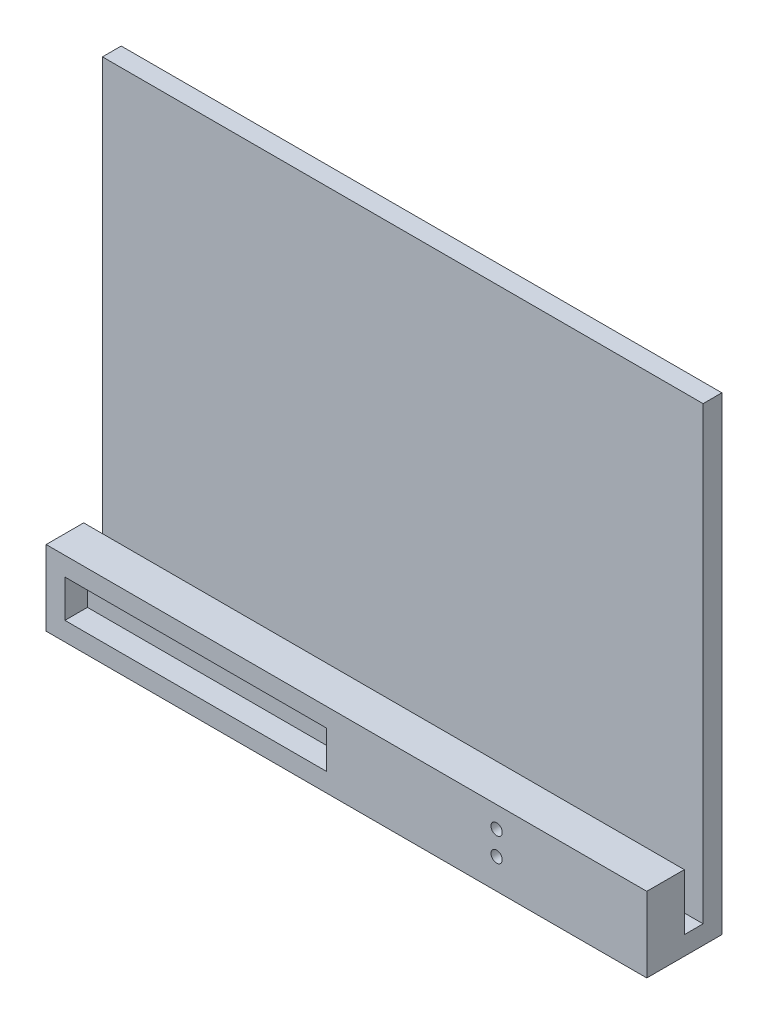
SolidWorks part; units mm, degrees
ref_plane "Front Plane" through (0, 0, 0) normal (0, 0, 1) x (1, 0, 0)
ref_plane "Top Plane" through (0, 0, 0) normal (0, 1, 0) x (1, 0, 0)
ref_plane "Right Plane" through (0, 0, 0) normal (1, 0, 0) x (0, 0, -1)
sketch "Sketch1" plane through (0, 0, 0) normal (0, 0, 1) x (1, 0, 0)
  line L1 (0, 158.75) -> (203.2, 158.75)
  line L2 (0, 158.75) -> (0, 0)
  line L3 (0, 0) -> (203.2, 0)
  line L4 (203.2, 158.75) -> (203.2, 0)
  point P4 (0, 0)
  dimension "D1" = 158.75
  dimension "D2" = 203.2
extrude "Boss-Extrude1" add sketch "Sketch1" along normal blind 6.35
sketch "Sketch2" plane through (0, 0, 6.35) normal (0, 0, 1) x (1, 0, 0)
  line L0 (0, 158.75) -> (0, 0) construction
  line L1 (0, 6.35) -> (203.2, 6.35)
  line L2 (0, 6.35) -> (0, 0)
  line L3 (0, 0) -> (203.2, 0)
  line L4 (203.2, 6.35) -> (203.2, 0)
  dimension "D1" = 6.35
extrude "Boss-Extrude2" add sketch "Sketch2" along normal blind 19.05
sketch "Sketch3" plane through (0, 6.35, 0) normal (0, 1, 0) x (1, 0, 0)
  line L6 (203.2, -25.4) -> (203.2, -6.35) construction
  line L7 (0, -25.4) -> (203.2, -25.4)
  line L8 (0, -25.4) -> (0, -12.7)
  line L9 (0, -12.7) -> (203.2, -12.7)
  line L10 (203.2, -25.4) -> (203.2, -12.7)
  dimension "D1" = 12.7
extrude "Boss-Extrude3" add sketch "Sketch3" along normal blind 19.05
sketch "Sketch4" plane through (0, 0, 25.4) normal (0, 0, 1) x (1, 0, 0)
  line L0 (0, 25.4) -> (0, 0) construction
  line L1 (6.35, 19.05) -> (94.9058, 19.05)
  line L2 (6.35, 19.05) -> (6.35, 6.35)
  line L3 (6.35, 6.35) -> (94.9058, 6.35)
  line L4 (94.9058, 19.05) -> (94.9058, 6.35)
  line L5 (0, 25.4) -> (203.2, 25.4) construction
  dimension "D1" = 6.35
  dimension "D2" = 12.7
  dimension "D3" = 6.35
extrude "Cut-Extrude1" cut sketch "Sketch4" against normal blind 7.62
sketch "Sketch5" plane through (0, 0, 25.4) normal (0, 0, 1) x (1, 0, 0)
  line L0 (152.4, 25.4) -> (152.4, 0) construction
  line L1 (0, 25.4) -> (203.2, 25.4) construction
  line L2 (0, 0) -> (203.2, 0) construction
  line L3 (203.2, 0) -> (203.2, 25.4) construction
  circle A0 centre (152.4, 18.1963) radius 1.905
  circle A1 centre (152.4, 10.16) radius 1.905
  point P12 (0, 0)
  dimension "D1" = 3.81
  dimension "D2" = 3.81
  dimension "D3" = 50.8
  dimension "D4" = 10.16
extrude "Cut-Extrude2" cut sketch "Sketch5" against normal up to next
